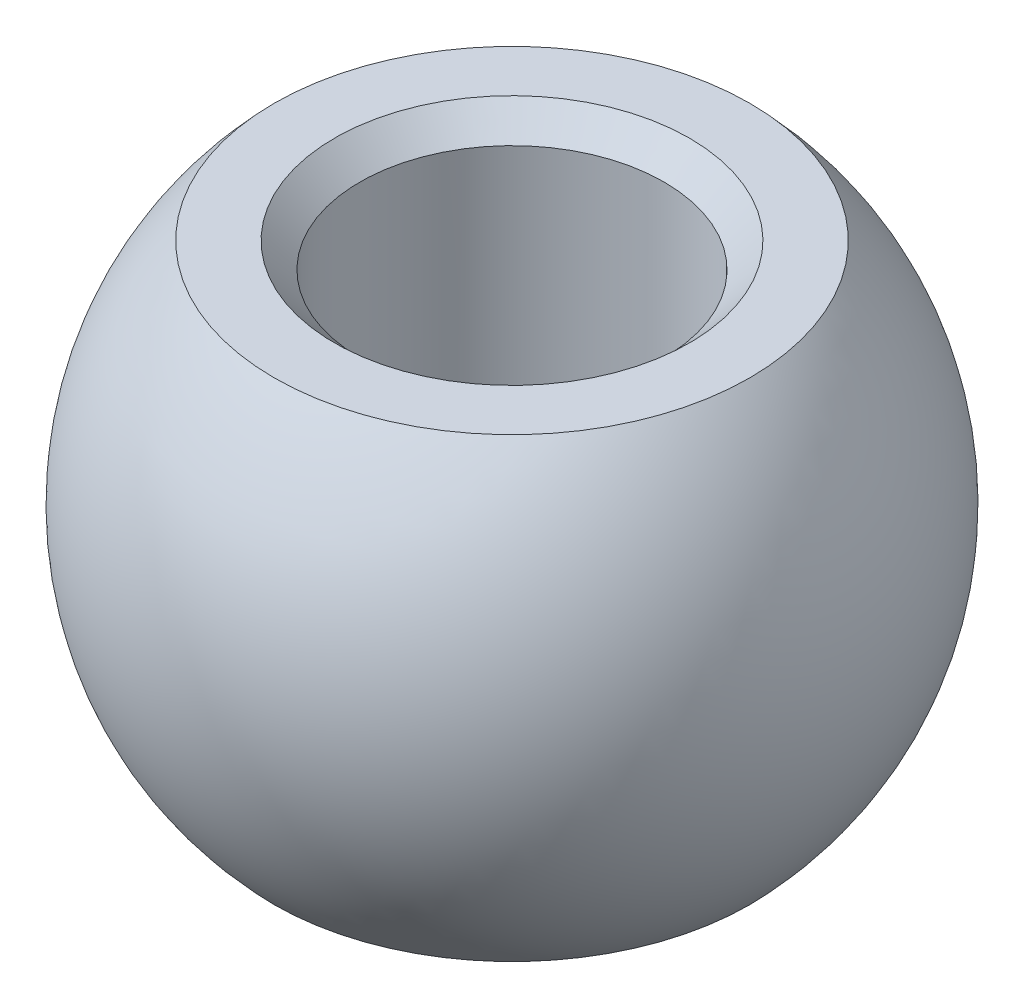
SolidWorks part; units mm, degrees
material "Acciaio al carbonio semplice"
ref_plane "Piano frontale" through (0, 0, 0) normal (0, 0, 1) x (1, 0, 0)
ref_plane "Piano superiore" through (0, 0, 0) normal (0, 1, 0) x (1, 0, 0)
ref_plane "Piano destro" through (0, 0, 0) normal (1, 0, 0) x (0, 0, -1)
sketch "Schizzo1" plane through (0, 0, 0) normal (0, 0, 1) x (1, 0, 0)
  line L0 (0, 8.5811) -> (0, -9.012) construction
  line L1 (0, 6.5) -> (0, -6.5)
  arc A0 (0, 6.5) -> (0, -6.5) centre (0, 0) ccw
revolve "Rivoluzione1" add sketch "Schizzo1" angle 360 about L0
sketch "Schizzo2" plane through (0, 0, 0) normal (0, 0, 1) x (1, 0, 0)
  line L1 (-7.1068, 6.8697) -> (7.4703, 6.8697)
  line L2 (-7.1068, 6.8697) -> (-7.1068, 4.5)
  line L3 (-7.1068, 4.5) -> (7.4703, 4.5)
  line L4 (7.4703, 6.8697) -> (7.4703, 4.5)
  line L5 (-7.1068, -4.5) -> (7.4703, -4.5)
  line L6 (-7.1068, -4.5) -> (-7.1068, -7.0851)
  line L7 (-7.1068, -7.0851) -> (7.4703, -7.0851)
  line L8 (7.4703, -4.5) -> (7.4703, -7.0851)
  dimension "D1" = 4.5
  dimension "D2" = 4.5
extrude "Taglio-Estrusione1" cut sketch "Schizzo2" against normal through all and the other way through all
sketch "Schizzo3" plane through (0, 4.5, 0) normal (0, 1, 0) x (-1, 0, 0)
  circle A0 centre (0, 0) radius 3
extrude "Taglio-Estrusione2" cut sketch "Schizzo3" against normal through all
chamfer "Smusso1" distance 0.5 angle 45 2 edges at (0, -4.5, 3) (0, 4.5, 3)
ref_axis "Axis1" through (0, -4, 0) along (0, 1, 0)
